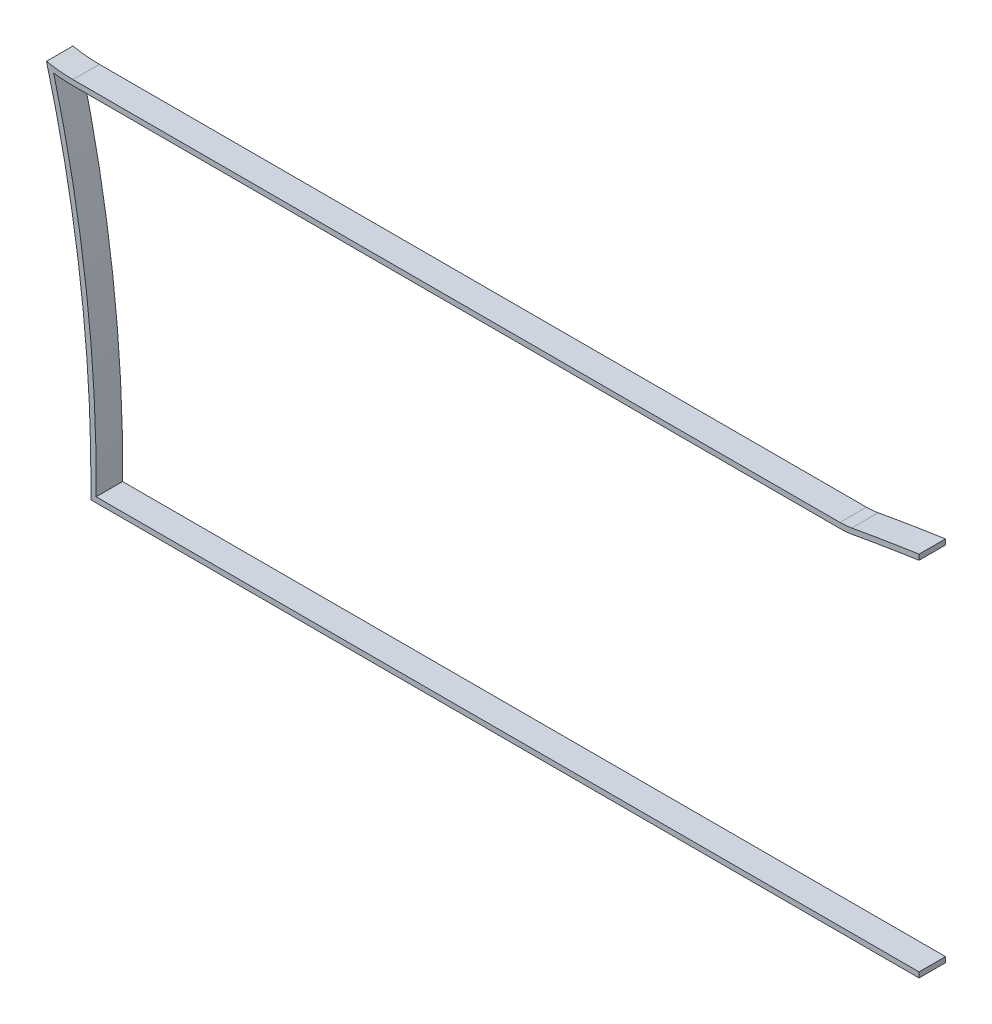
SolidWorks part; units mm, degrees
ref_plane "Front Plane" through (0, 0, 0) normal (0, 0, 1) x (1, 0, 0)
ref_plane "Top Plane" through (0, 0, 0) normal (0, 1, 0) x (1, 0, 0)
ref_plane "Right Plane" through (0, 0, 0) normal (1, 0, 0) x (0, 0, -1)
ref_plane "Plane1" through (0, 0, -4) normal (0, 0, 1) x (1, 0, 0)
sketch "BASE DASH IF PROFILE" plane through (0, 0, -4) normal (0, 0, 1) x (1, 0, 0)
  line L0 (-300, 17.25) -> (-9.9069, 17.25)
  line L1 (-6, 3.25) -> (6, 3.25) construction
  line L2 (-291, 3.25) -> (-279, 3.25) construction
  line L3 (-291, -3.25) -> (-279, -3.25) construction
  line L4 (-284.25, -77) -> (-284.25, -89) construction
  line L5 (-293.2421, -117) -> (-30.25, -117)
  line L6 (-277.75, -77) -> (-277.75, -89) construction
  line L7 (31.75, -81) -> (31.75, -93) construction
  line L8 (31.75, -93) -> (38.25, -93) construction
  line L9 (218.75, -90) -> (225.25, -90) construction
  line L10 (374.75, -80) -> (381.25, -80) construction
  line L11 (381.25, -68) -> (381.25, -80) construction
  line L12 (332, -9.75) -> (344, -9.75) construction
  line L13 (344, -9.75) -> (344, -16.25) construction
  line L14 (184, 13.25) -> (184, 6.75) construction
  line L15 (32, 5.25) -> (44, 5.25) construction
  line L16 (400.3845, -86.8478) -> (365.7956, -13.2095)
  line L17 (172, 13.25) -> (184, 13.25) construction
  line L18 (-30.25, -117) -> (35, -117)
  arc A0 (-300, 17.25) -> (-310, 18.25) centre (-300, 67.75) cw
  arc A1 (-310, 18.25) -> (-293.25, -103) centre (-793.197, -110.2829) cw
  arc A2 (-293.2421, -117) -> (-293.25, -103) centre (-793.197, -110.2829) ccw
  arc A3 (401, -89) -> (394.5578, -96.8053) centre (394.0486, -89.8238) cw
  arc A4 (394.5578, -96.8053) -> (35, -117) centre (-390.0429, 10661.6695) cw
  arc A5 (401, -89) -> (400.3845, -86.8478) centre (394.0486, -89.8238) ccw
  arc A6 (-5.465, 17.6478) -> (349.996, 0.2111) centre (134.6308, -758.2832) cw
  arc A7 (365.7956, -13.2095) -> (349.996, 0.2111) centre (343.1675, -23.8383) ccw
  arc A8 (-5.465, 17.6478) -> (-9.9069, 17.25) centre (-9.9069, 42.25) cw
  point P9 (-285, 3.25)
  point P10 (-310, 18.25)
  point P11 (-285, -3.25)
  point P14 (-293.25, -103)
  point P17 (-284.25, -83)
  point P24 (-277.75, -83)
  point P29 (35, -117)
  point P32 (35, -93)
  point P33 (222, -108)
  point P36 (222, -90)
  point P37 (378, -98)
  point P40 (378, -80)
  point P41 (401, -89)
  point P43 (381.25, -74)
  point P44 (361, -3)
  point P47 (338, -9.75)
  point P50 (344, -13)
  point P51 (178, 29)
  point P54 (184, 10)
  point P55 (38, 24.25)
  point P58 (38, 5.25)
  point P70 (361, -3)
  point P75 (178, 13.25)
  dimension "D8" = 500
  dimension "D20" = 7
  dimension "D21" = 25
  dimension "D22" = 25
  dimension "D1" = 14
  dimension "D3" = 15
  dimension "D4" = 25
  dimension "D5" = 15
  dimension "D6" = 9
  dimension "D7" = 20
  dimension "D9" = 34
  dimension "D10" = 62
  dimension "D11" = 24
  dimension "D12" = 18
  dimension "D13" = 18
  dimension "D14" = 23
  dimension "D15" = 15
  dimension "D16" = 23
  dimension "D17" = 10
  dimension "D18" = 19
  dimension "D19" = 19
sketch "Sketch2" plane through (0, 0, -4) normal (0, 0, 1) x (1, 0, 0)
  line L0 (-300, 17.25) -> (-9.9069, 17.25) construction
  line L1 (400.3845, -86.8478) -> (365.7956, -13.2095) construction
  line L2 (-30.25, -117) -> (35, -117) construction
  line L3 (-293.2421, -117) -> (-30.25, -117) construction
  line L4 (-300, 17.25) -> (-9.9069, 17.25)
  line L5 (400.3845, -86.8478) -> (365.7956, -13.2095)
  line L6 (-30.25, -117) -> (35, -117)
  line L7 (-293.2421, -117) -> (-30.25, -117)
  line L8 (-300, 15.25) -> (-9.9069, 15.25)
  line L9 (398.5743, -87.6981) -> (363.9853, -14.0598)
  line L10 (-30.25, -115) -> (34.9606, -115)
  line L11 (-291.2191, -115) -> (-30.25, -115)
  arc A0 (-9.9069, 17.25) -> (-5.465, 17.6478) centre (-9.9069, 42.25) ccw construction
  arc A1 (349.996, 0.2111) -> (-5.465, 17.6478) centre (134.6308, -758.2832) ccw construction
  arc A2 (365.7956, -13.2095) -> (349.996, 0.2111) centre (343.1675, -23.8383) ccw construction
  arc A3 (401, -89) -> (400.3845, -86.8478) centre (394.0486, -89.8238) ccw construction
  arc A4 (394.5578, -96.8053) -> (401, -89) centre (394.0486, -89.8238) ccw construction
  arc A5 (35, -117) -> (394.5578, -96.8053) centre (-390.0429, 10661.6695) ccw construction
  arc A6 (-293.2421, -117) -> (-293.25, -103) centre (-793.197, -110.2829) ccw construction
  arc A7 (-293.25, -103) -> (-310, 18.25) centre (-793.197, -110.2829) ccw construction
  arc A8 (-310, 18.25) -> (-300, 17.25) centre (-300, 67.75) ccw construction
  arc A9 (-9.9069, 17.25) -> (-5.465, 17.6478) centre (-9.9069, 42.25) ccw
  arc A10 (349.996, 0.2111) -> (-5.465, 17.6478) centre (134.6308, -758.2832) ccw
  arc A11 (365.7956, -13.2095) -> (349.996, 0.2111) centre (343.1675, -23.8383) ccw
  arc A12 (401, -89) -> (400.3845, -86.8478) centre (394.0486, -89.8238) ccw
  arc A13 (394.5578, -96.8053) -> (401, -89) centre (394.0486, -89.8238) ccw
  arc A14 (35, -117) -> (394.5578, -96.8053) centre (-390.0429, 10661.6695) ccw
  arc A15 (-293.2421, -117) -> (-293.25, -103) centre (-793.197, -110.2829) ccw
  arc A16 (-293.25, -103) -> (-310, 18.25) centre (-793.197, -110.2829) ccw
  arc A17 (-310, 18.25) -> (-300, 17.25) centre (-300, 67.75) ccw
  arc A18 (-9.9069, 15.25) -> (-5.1096, 15.6796) centre (-9.9069, 42.25) ccw
  arc A19 (349.4497, -1.7129) -> (-5.1096, 15.6796) centre (134.6308, -758.2832) ccw
  arc A20 (363.9853, -14.0598) -> (349.4497, -1.7129) centre (343.1675, -23.8383) ccw
  arc A21 (399.0139, -89.2354) -> (398.5743, -87.6981) centre (394.0486, -89.8238) ccw
  arc A22 (394.4123, -94.8106) -> (399.0139, -89.2354) centre (394.0486, -89.8238) ccw
  arc A23 (34.9606, -115) -> (394.4123, -94.8106) centre (-390.0429, 10661.6695) ccw
  arc A24 (-291.2191, -115) -> (-291.2502, -102.9709) centre (-793.197, -110.2829) ccw
  arc A25 (-291.2502, -102.9709) -> (-307.2772, 15.7568) centre (-793.197, -110.2829) ccw
  arc A26 (-307.2772, 15.7568) -> (-300, 15.25) centre (-300, 67.75) ccw
  dimension "D1" = 2
extrude "Boss-Extrude1" add sketch "Sketch2" along normal blind 10
ref_plane "Plane2" through (20, 0, 0) normal (1, 0, 0) x (0, 0, -1)
sketch "Sketch3" plane through (20, 0, 0) normal (1, 0, 0) x (0, 0, -1)
  line L1 (-100.4265, 88.1761) -> (108.3196, 88.1761)
  line L2 (-100.4265, 88.1761) -> (-100.4265, -186.3596)
  line L3 (-100.4265, -186.3596) -> (108.3196, -186.3596)
  line L4 (108.3196, 88.1761) -> (108.3196, -186.3596)
extrude "Cut-Extrude1" cut sketch "Sketch3" along normal through all
